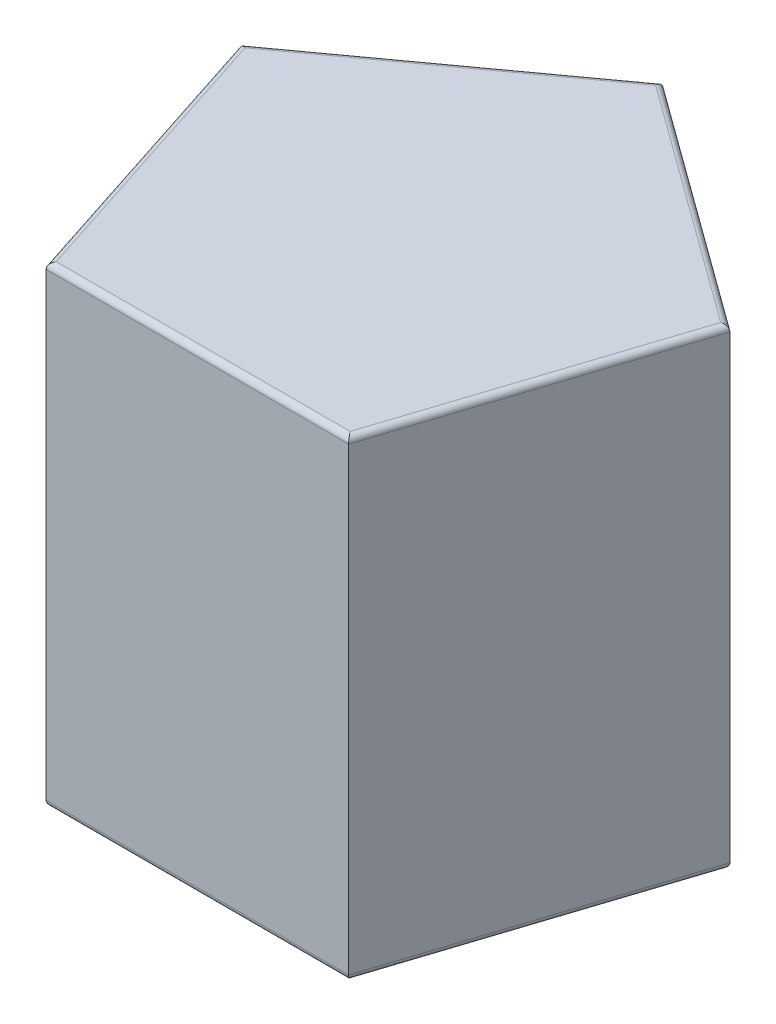
SolidWorks part; units mm, degrees
ref_plane "Front Plane" through (0, 0, 0) normal (0, 0, 1) x (1, 0, 0)
ref_plane "Top Plane" through (0, 0, 0) normal (0, 1, 0) x (1, 0, 0)
ref_plane "Right Plane" through (0, 0, 0) normal (1, 0, 0) x (0, 0, -1)
sketch "Sketch1" plane through (0, 0, 0) normal (0, 1, 0) x (1, 0, 0)
  line L1 (0, 21.8351) -> (-20.7664, 6.7474)
  line L2 (-20.7664, 6.7474) -> (-12.8343, -17.6649)
  line L3 (-12.8343, -17.6649) -> (12.8343, -17.6649)
  line L4 (12.8343, -17.6649) -> (20.7664, 6.7474)
  line L5 (20.7664, 6.7474) -> (0, 21.8351)
  circle A0 centre (0, 0) radius 17.6649 construction
  dimension "D1" = 39.5
extrude "Boss-Extrude1" add sketch "Sketch1" along normal blind 40
fillet "Fillet1" radius 0.5 10 edges at (-10.3832, 0, -14.2912) (-16.8004, 0, 5.4588) (0, 0, 17.6649) (16.8004, 0, 5.4588) (10.3832, 0, -14.2912) (16.8004, 40, 5.4588) (0, 40, 17.6649) (-16.8004, 40, 5.4588) (-10.3832, 40, -14.2912) (10.3832, 40, -14.2912)
